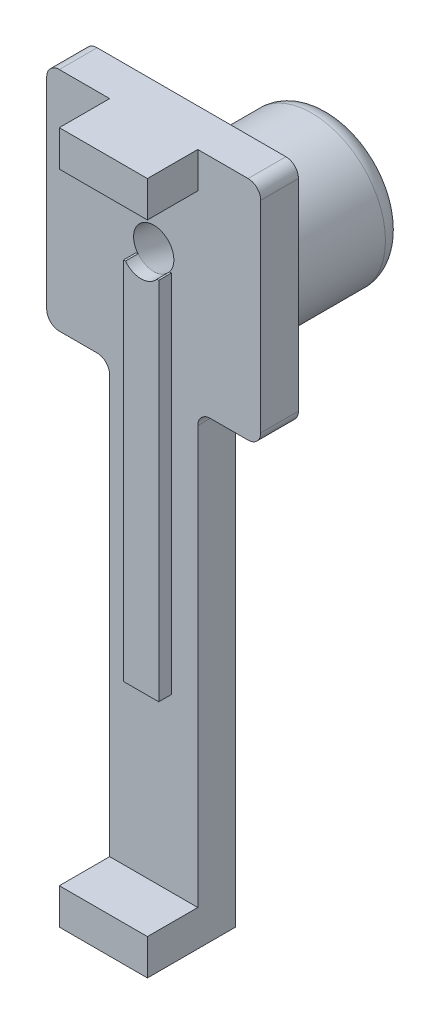
SolidWorks part; units mm, degrees
ref_plane "Front Plane" through (0, 0, 0) normal (0, 0, 1) x (1, 0, 0)
ref_plane "Top Plane" through (0, 0, 0) normal (0, 1, 0) x (1, 0, 0)
ref_plane "Right Plane" through (0, 0, 0) normal (1, 0, 0) x (0, 0, -1)
sketch "Sketch1" plane through (0, 0, 0) normal (0, 0, 1) x (1, 0, 0)
  line L1 (1.5, -15) -> (-1.5, -15)
  line L2 (1.5, -15) -> (1.5, 15)
  line L3 (1.5, 15) -> (-1.5, 15)
  line L4 (-1.5, -15) -> (-1.5, 15)
  line L5 (1.5, -15) -> (-1.5, 15) construction
  line L6 (1.5, 15) -> (-1.5, -15) construction
  line L7 (3.5, -18.4549) -> (-3.5, -18.4549)
  line L8 (3.5, -18.4549) -> (3.5, 36.5451)
  line L9 (3.5, 36.5451) -> (-3.5, 36.5451)
  line L10 (-3.5, -18.4549) -> (-3.5, 36.5451)
  line L11 (3.5, -18.4549) -> (-3.5, 36.5451) construction
  line L12 (3.5, 36.5451) -> (-3.5, -18.4549) construction
  point P0 (0, 0)
  point P6 (0, 9.0451)
  dimension "D1" = 3
  dimension "D2" = 30
  dimension "D3" = 55
  dimension "D4" = 7
extrude "Boss-Extrude1" add sketch "Sketch1" along normal blind 3 contours L10 L7 L8 L9 L1 L4 L3 L2 | L4 L1 L2 L3 region at (0, 0, 0) region at (0, -17.9005, 0)
sketch "Sketch2" plane through (0, 0, 3) normal (0, 0, 1) x (1, 0, 0)
  line L0 (3.5, -18.4549) -> (-3.5, -18.4549) construction
  line L1 (0, -2.0049) -> (0, -18.4549) construction
  line L16 (-1.4, -2.0049) -> (1.4, -2.0049)
  line L17 (-1.4, 26.9951) -> (-1.4, -2.0049)
  line L18 (1.4, 26.9951) -> (-1.4, 26.9951)
  line L19 (1.4, -2.0049) -> (1.4, 26.9951)
  point P0 (0, -2.0049)
  dimension "D1" = 16.45
  dimension "D2" = 29
  dimension "D3" = 2.8
extrude "Boss-Extrude2" add sketch "Sketch2" along normal blind 1
sketch "Sketch3" plane through (0, 0, 3) normal (0, 0, 1) x (1, 0, 0)
  line L0 (3.5, -18.4549) -> (3.5, 36.5451) construction
  line L1 (-3.5, 36.5451) -> (3.5, 36.5451)
  line L2 (-3.5, 36.5451) -> (-3.5, 33.6951)
  line L3 (-3.5, 33.6951) -> (3.5, 33.6951)
  line L4 (3.5, 36.5451) -> (3.5, 33.6951)
  line L5 (-3.5, -18.4549) -> (-3.5, 36.5451) construction
  line L6 (3.5, -18.4549) -> (-3.5, -18.4549)
  line L7 (3.5, -18.4549) -> (3.5, -15.6049)
  line L8 (3.5, -15.6049) -> (-3.5, -15.6049)
  line L9 (-3.5, -18.4549) -> (-3.5, -15.6049)
  dimension "D1" = 2.85
  dimension "D2" = 2.85
extrude "Boss-Extrude3" add sketch "Sketch3" along normal blind 4
sketch "Sketch4" plane through (-3.5, 0, 0) normal (-1, 0, 0) x (0, 0, 1)
  line L0 (3, -15.6049) -> (3, 33.6951) construction
  line L1 (0, 36.5451) -> (3, 36.5451)
  line L2 (0, 36.5451) -> (0, 18.5451)
  line L3 (0, 18.5451) -> (3, 18.5451)
  line L4 (3, 36.5451) -> (3, 18.5451)
  dimension "D1" = 18
extrude "Boss-Extrude4" add sketch "Sketch4" along normal blind 5
sketch "Sketch5" plane through (3.5, 0, 0) normal (1, 0, 0) x (0, 0, -1)
  line L4 (0, 36.5451) -> (-3, 36.5451)
  line L5 (-3, 36.5451) -> (-3, 18.5451)
  line L6 (-3, 18.5451) -> (0, 18.5451)
  line L7 (0, 18.5451) -> (0, 36.5451)
  line L8 (0, 36.5451) -> (-3, 36.5451)
  line L9 (-3, 36.5451) -> (-3, 18.5451)
  line L10 (-3, 18.5451) -> (0, 18.5451)
  line L11 (0, 18.5451) -> (0, 36.5451)
  dimension "D1" = 0
extrude "Boss-Extrude5" add sketch "Sketch5" along normal blind 5
sketch "Sketch7" plane through (0, 0, 3) normal (0, 0, 1) x (1, 0, 0)
  line L0 (-1.4, -2.0049) -> (1.4, -2.0049) construction
  circle A0 centre (0, 27.9951) radius 1.6
  dimension "D1" = 3.2
  dimension "D2" = 30
sketch "Sketch9" plane through (0, 0, 0) normal (0, 0, -1) x (-1, 0, 0)
  line L0 (0, 36.5451) -> (0, -18.4549) construction
  line L1 (-8.5, 36.5451) -> (8.5, 36.5451) construction
  line L2 (-3.5, -18.4549) -> (3.5, -18.4549) construction
  circle A0 centre (0, 25.1701) radius 5.85
  dimension "D1" = 11.7
  dimension "D2" = 11.375
extrude "Boss-Extrude7" add sketch "Sketch9" along normal blind 11.06
sketch "Sketch10" plane through (0, 0, -11.06) normal (0, 0, -1) x (-1, 0, 0)
  line L0 (0, 31.0201) -> (0, 19.3201)
  line L1 (-5.0662, 28.0951) -> (5.0662, 22.2451)
  line L2 (5.0662, 28.0951) -> (-5.0662, 22.2451)
  circle A3 centre (0, 25.1701) radius 5.85
  circle A4 centre (0, 25.1701) radius 5.85 construction
  dimension "D1" = 60
  dimension "D2" = 60
fillet "Fillet1" radius 1.5 1 edges at (-5.85, 25.1701, -11.06)
fillet "Fillet2" radius 1 6 edges at (-3.5, 18.5451, 1.5) (-8.5, 18.5451, 1.5) (-8.5, 36.5451, 1.5) (8.5, 36.5451, 1.5) (8.5, 18.5451, 1.5) (3.5, 18.5451, 1.5)
sketch "Sketch11" plane through (0, 0, -11.06) normal (0, 0, -1) x (-1, 0, 0)
  circle A0 centre (0, 25.1701) radius 3.4369
ref_plane "Plane1" through (0, 0, 0) normal (1, 0, 0) x (0, 0, -1)
loft "Cut-Loft6" cut profiles "Sketch11", "Sketch7" connector at (-1.5699, 28.2275, -11.06) connector at (0.7567, 29.4049, 3)
sketch "Sketch18" plane through (0, 0, 3) normal (0, 0, -1) x (-1, 0, 0)
  line L1 (1.2491, 26.9951) -> (-1.2488, 26.9951)
  line L2 (1.2491, 26.9951) -> (-1.2488, 26.9951)
  arc A0 (-1.2488, 26.9951) -> (1.2491, 26.9951) centre (0.0002, 27.9951) ccw
  arc A1 (-1.2488, 26.9951) -> (1.2491, 26.9951) centre (0.0002, 27.9951) ccw
  dimension "D1" = 0
extrude "Cut-Extrude1" cut sketch "Sketch18" against normal blind 10
sketch "Sketch19" plane through (0, 0, 0) normal (0, 0, -1) x (-1, 0, 0)
  line L0 (-3.5, -18.4549) -> (3.5, -18.4549) construction
  line L1 (3.5, -18.4549) -> (3.5, 17.5451) construction
  circle A0 centre (0, -16.4549) radius 0.5
  circle A1 centre (0, -14.4549) radius 0.5
  point P4 (0, 0)
  point P5 (0, 0)
  point P10 (0, 0)
  point P12 (-4.1584, -17.475)
  dimension "D1" = 2
  dimension "D2" = 2
  dimension "D3" = 3.5
extrude "Cut-Extrude2" cut sketch "Sketch19" against normal blind 2.5
